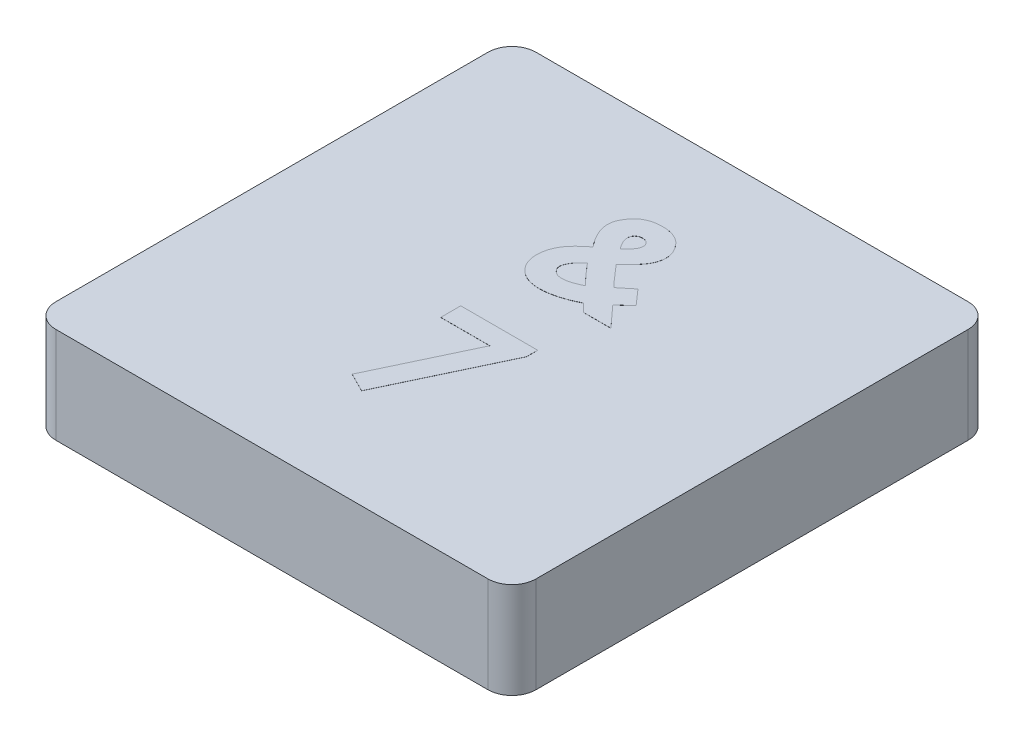
SolidWorks part; units mm, degrees
ref_plane "Front Plane" through (0, 0, 0) normal (0, 0, 1) x (1, 0, 0)
ref_plane "Top Plane" through (0, 0, 0) normal (0, 1, 0) x (1, 0, 0)
ref_plane "Right Plane" through (0, 0, 0) normal (1, 0, 0) x (0, 0, -1)
sketch "Sketch1" plane through (0, 0, 0) normal (0, 1, 0) x (1, 0, 0)
  line L0 (0, 0) -> (12.7, 0)
  line L1 (12.7, 0) -> (12.7, 12.7)
  line L2 (12.7, 12.7) -> (0, 12.7)
  line L3 (0, 12.7) -> (0, 0)
  dimension "D1" = 12.7
  dimension "D2" = 12.7
extrude "Boss-Extrude1" add sketch "Sketch1" along normal blind 2.54
fillet "Fillet1" radius 0.635 4 edges at (0, 1.27, -12.7) (12.7, 1.27, -12.7) (12.7, 1.27, 0) (0, 1.27, 0)
shell "Shell1" thickness 0.635 removed face at (6.35, 0, -6.35)
sketch "Sketch2" plane through (0, 1.905, 0) normal (0, -1, 0) x (-1, 0, 0)
  line L0 (-0.635, 6.35) -> (-12.065, 6.35) construction
  line L1 (-0.635, 12.065) -> (-0.635, 0.635) construction
  line L2 (-12.065, 0.635) -> (-12.065, 12.065) construction
  line L3 (-6.35, 0.635) -> (-6.35, 12.065) construction
  line L4 (-0.635, 0.635) -> (-12.065, 0.635) construction
  line L5 (-12.065, 12.065) -> (-0.635, 12.065) construction
  circle A0 centre (-6.35, 6.35) radius 2.54
  dimension "D1" = 5.08
extrude "Boss-Extrude2" add sketch "Sketch2" along normal up to surface (1.905 mm away) up to face at (6.35, 0, -6.35)
sketch "Sketch4" plane through (0, 2.54, 0) normal (0, 1, 0) x (1, 0, 0)
  line L0 (0, 12.065) -> (0, 0.635) construction
  line L1 (12.065, 12.7) -> (0.635, 12.7) construction
  line L2 (0.635, 0) -> (12.065, 0) construction
  text T0 "<b>7</b>"
  text T1 "<b>&</b>"
  dimension "D1" = 5.08
  dimension "D2" = 5.207
  dimension "D3" = 5.334
  dimension "D4" = 2.7178
extrude "Boss-Extrude4" add sketch "Sketch4" along normal blind 0.0025
